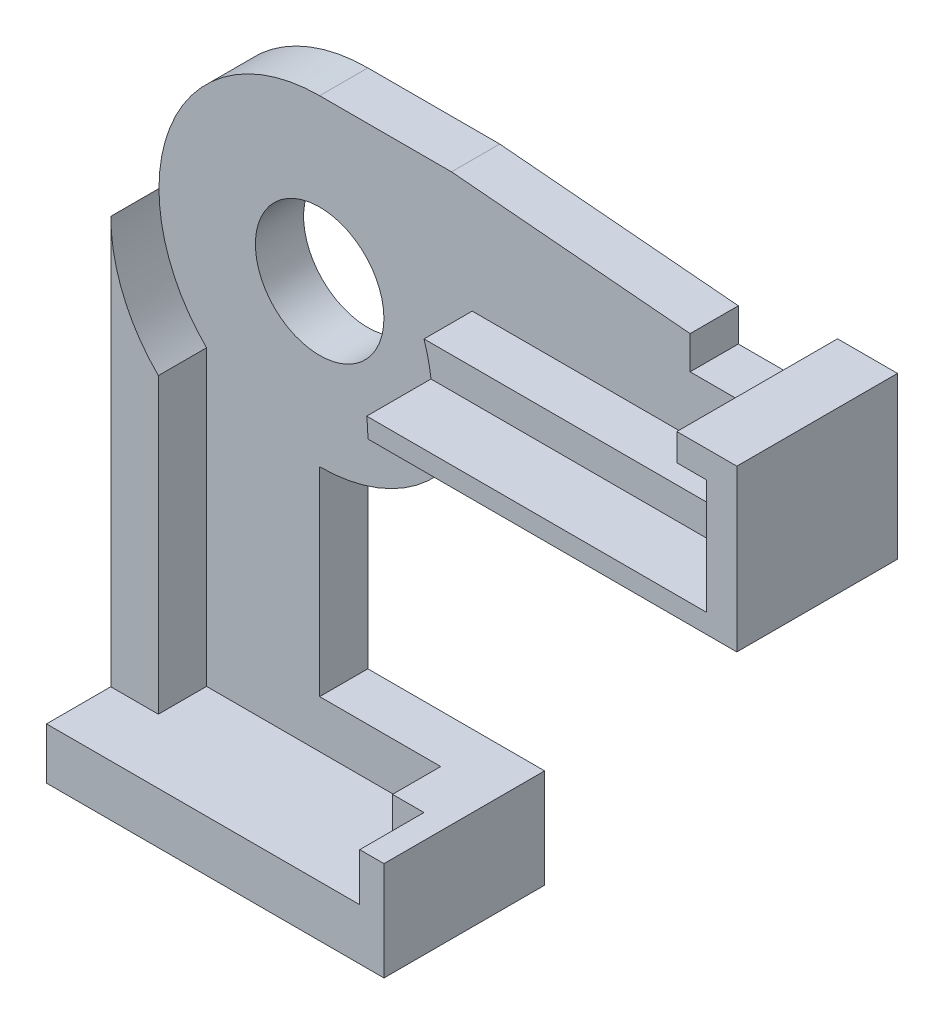
SolidWorks part; units mm, degrees
ref_plane "정면" through (0, 0, 0) normal (0, 0, 1) x (1, 0, 0)
ref_plane "윗면" through (0, 0, 0) normal (0, 1, 0) x (1, 0, 0)
ref_plane "우측면" through (0, 0, 0) normal (1, 0, 0) x (0, 0, -1)
sketch "스케치1" plane through (0, 0, 0) normal (0, 0, 1) x (1, 0, 0)
  line L0 (0, 5) -> (4.1032, 5)
  line L1 (4.1032, 5) -> (11.5291, 4.354)
  line L2 (11.5291, 4.354) -> (11.5291, 3.3234)
  line L3 (11.5291, 3.3234) -> (14.6163, 3.3234)
  line L4 (14.6163, 3.3234) -> (14.6163, 5.0082)
  line L5 (14.6163, 5.0082) -> (16.4819, 5.0082)
  line L6 (16.4819, 5.0082) -> (16.4819, 0)
  line L7 (16.4819, 0) -> (5, 0)
  line L8 (-5, 0) -> (-5, -14.2767)
  line L9 (-5, -14.2767) -> (5.5012, -14.2767)
  line L10 (5.5012, -14.2767) -> (5.5012, -11.1942)
  line L11 (5.5012, -11.1942) -> (0, -11.1942)
  line L12 (0, -11.1942) -> (0, -5)
  line L13 (-3.5192, -3.5518) -> (-3.5192, -12.6782)
  line L14 (-3.5192, -12.6782) -> (3.7674, -12.6782)
  line L15 (3.7674, -12.6782) -> (3.7674, -11.1942)
  line L16 (4.7473, 1.5694) -> (14.6163, 1.5694)
  line L17 (14.6163, 1.5694) -> (14.6163, 3.3234)
  line L18 (14.6163, 4.1658) -> (15.5422, 4.1658)
  line L19 (15.5422, 4.1658) -> (15.5422, 0.5975)
  line L20 (15.5422, 0.5975) -> (4.9642, 0.5975)
  line L21 (-5, -12.6782) -> (-3.5192, -12.6782)
  line L22 (3.7674, -12.6782) -> (4.7473, -12.6782)
  line L23 (4.7473, -12.6782) -> (4.7473, -11.1942)
  circle A0 centre (0, 0) radius 2
  circle A1 centre (0, 0) radius 5
  dimension "D1" = 4
  dimension "D2" = 10
extrude "보스-돌출1" add sketch "스케치1" along normal blind 1.5 contours A1 A0 | A1 L13 L14 L15 L11 L12 | A1 L16 L17 L3 L2 L1 L0 region at (8.2995, 3.1329, 0) region at (2.8457, 3.938, 0) region at (-1.2061, -9.1478, 0)
extrude "보스-돌출2" add sketch "스케치1<3>" along normal blind 3 contours A1 L8 L21 L13 | A1 L20 L19 L18 L4 L17 L16 | L22 L23 L11 L15 region at (11.1242, 1.4205, 0) region at (-4.2931, -7.53, 0) region at (4.2574, -11.9362, 0)
sketch "스케치1<3>" plane through (0, 0, 0) normal (0, 0, 1) x (1, 0, 0) same geometry as "스케치1"
extrude "보스-돌출3" add sketch "스케치1<4>" along normal blind 5 contours L23 L22 L14 L21 L8 L9 L10 L11 | A1 L7 L6 L5 L4 L18 L19 L20 region at (10.2532, 0.4719, 0) region at (0.5551, -13.3811, 0)
sketch "스케치1<4>" plane through (0, 0, 0) normal (0, 0, 1) x (1, 0, 0) same geometry as "스케치1"
